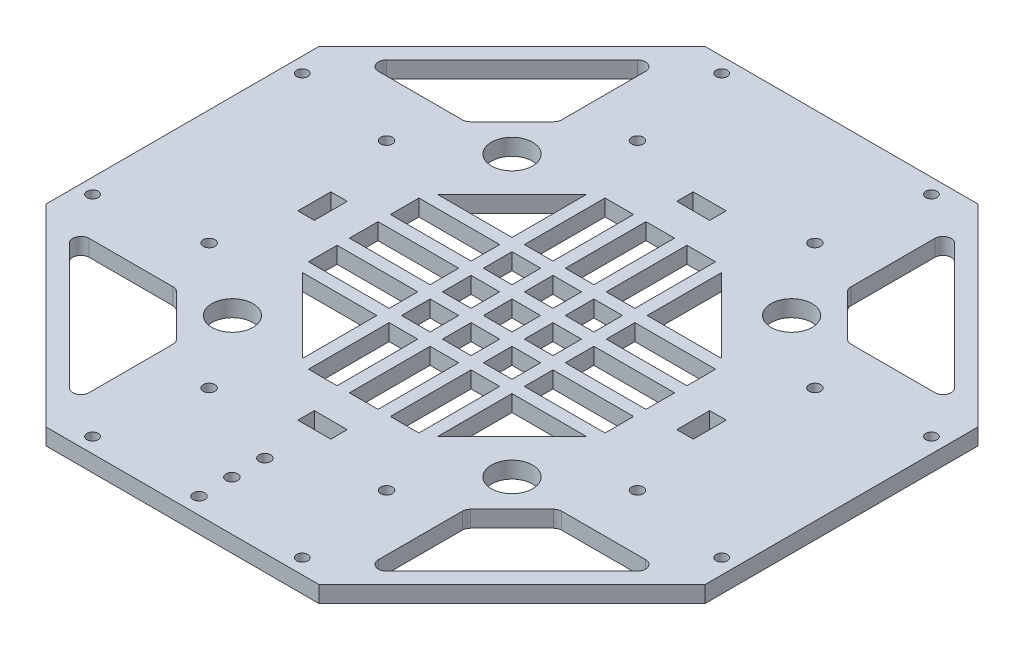
SolidWorks part; units mm, degrees
material "Custom Plastic"
ref_plane "Front Plane" through (0, 0, 0) normal (0, 0, 1) x (1, 0, 0)
ref_plane "Top Plane" through (0, 0, 0) normal (0, 1, 0) x (1, 0, 0)
ref_plane "Right Plane" through (0, 0, 0) normal (1, 0, 0) x (0, 0, -1)
ref_axis "Axis1" through (0, -0.2997, 0) along (0, 1, 0)
sketch "Base sketch" plane through (0, 0, 0) normal (0, 1, 0) x (1, 0, 0)
  line L1 (-127, 52.6051) -> (-127, -52.6051)
  line L2 (-127, -52.6051) -> (-52.6051, -127)
  line L3 (-52.6051, -127) -> (52.6051, -127)
  line L4 (52.6051, -127) -> (127, -52.6051)
  line L5 (127, -52.6051) -> (127, 52.6051)
  line L6 (127, 52.6051) -> (52.6051, 127)
  line L7 (52.6051, 127) -> (-52.6051, 127)
  line L8 (-52.6051, 127) -> (-127, 52.6051)
  circle A0 centre (0, 0) radius 127 construction
  dimension "D1" = 254
extrude "Base" add sketch "Base sketch" along normal blind 6.35
sketch "Sketch3" plane through (0, 6.35, 0) normal (0, 1, 0) x (1, 0, 0)
  line L0 (52.6051, 127) -> (-52.6051, 127) construction
  line L1 (-34.925, 114.3) -> (34.925, 114.3)
  line L2 (-34.925, 114.3) -> (-34.925, 79.375)
  line L4 (-34.925, 79.375) -> (34.925, 79.375)
  line L5 (34.925, 114.3) -> (34.925, 79.375)
  point P6 (0, 79.375)
  dimension "D1" = 69.85
  dimension "D2" = 34.925
  dimension "D3" = 12.7
sketch "Sketch4" plane through (0, 6.35, 0) normal (0, 1, 0) x (1, 0, 0)
  line L0 (0, 0) -> (0, 127) construction
  line L1 (52.6051, 127) -> (-52.6051, 127) construction
  line L4 (-6.35, 69.85) -> (6.35, 69.85)
  line L5 (-6.35, 69.85) -> (-6.35, 76.2)
  line L6 (-6.35, 76.2) -> (6.35, 76.2)
  line L7 (6.35, 69.85) -> (6.35, 76.2)
  line L8 (-6.35, 69.85) -> (6.35, 76.2) construction
  line L10 (-6.35, 76.2) -> (6.35, 69.85) construction
  point P5 (0, 73.025)
  dimension "D1" = 6.35
  dimension "D2" = 12.7
  dimension "D3" = 53.975
extrude "Support cutouts" cut sketch "Sketch4" against normal up to next
pattern_circular "Support cutout pattern" count 4 over 360 about axis through (0, -0.2997, 0) along (0, 1, 0) of "Support cutouts"
sketch "Sketch11" plane through (0, 6.35, 0) normal (0, 1, 0) x (1, 0, 0)
  line L1 (95.25, 39.4538) -> (39.4538, 95.25) construction
  line L2 (39.4538, 95.25) -> (-39.4538, 95.25) construction
  line L3 (-39.4538, 95.25) -> (-95.25, 39.4538) construction
  line L4 (-95.25, 39.4538) -> (-95.25, -39.4538) construction
  line L5 (-95.25, -39.4538) -> (-39.4538, -95.25) construction
  line L6 (-39.4538, -95.25) -> (39.4538, -95.25) construction
  line L7 (39.4538, -95.25) -> (95.25, -39.4538) construction
  line L8 (95.25, -39.4538) -> (95.25, 39.4538) construction
  line L9 (-34.1933, 82.55) -> (-82.55, 34.1933)
  line L10 (-82.55, 34.1933) -> (-82.55, -34.1933)
  line L11 (-82.55, -34.1933) -> (-34.1933, -82.55)
  line L12 (-34.1933, -82.55) -> (34.1933, -82.55)
  line L13 (34.1933, -82.55) -> (82.55, -34.1933)
  line L14 (82.55, -34.1933) -> (82.55, 34.1933)
  line L15 (82.55, 34.1933) -> (34.1933, 82.55)
  line L16 (34.1933, 82.55) -> (-34.1933, 82.55)
  circle A0 centre (0, 0) radius 95.25 construction
  circle A1 centre (0, 0) radius 82.55 construction
  dimension "D1" = 190.5
  dimension "D2" = 12.7
hole_wizard "#8 Clearance Hole1" positions "Sketch13" profile "Sketch12" hole size "#8" standard "ANSI Inch" end condition through all
sketch "Sketch13" plane through (0, 6.35, 0) normal (0, 1, 0) x (1, 0, 0)
  point P0 (-82.55, 34.1933)
  point P3 (-34.1933, 82.55)
  point P6 (34.1933, 82.55)
  point P9 (82.55, 34.1933)
  point P12 (82.55, -34.1933)
  point P15 (34.1933, -82.55)
  point P18 (-34.1933, -82.55)
  point P21 (-82.55, -34.1933)
sketch "Sketch12" plane through (-82.55, 6.35, -34.1933) normal (1, 0, 0) x (0, 0, 1)
  line L0 (0, 0) -> (0, 6.35)
  line L1 (0, 6.35) -> (2.2479, 6.35)
  line L2 (2.2479, 6.35) -> (2.2479, 0)
  line L5 (2.2479, 0) -> (0, 0)
  line L11 (0, -6.35) -> (0, 107.95) construction
  dimension "Thru Hole Dia." = 4.4958
  dimension "Thru Hole Depth" = 6.35
sketch "Sketch14" plane through (0, 6.35, 0) normal (0, 1, 0) x (1, 0, 0)
  circle A0 centre (-53.8815, 53.8815) radius 7.9375
  circle A1 centre (53.8815, 53.8815) radius 7.9375
  circle A2 centre (53.8815, -53.8815) radius 7.9375
  circle A3 centre (-53.8815, -53.8815) radius 7.9375
  point P13 (0, 0)
  dimension "D2" = 15.875
  dimension "D1" = 76.2
  dimension "D3" = 4
extrude "Cable holes" cut sketch "Sketch14" against normal up to next
sketch "Sketch15" plane through (0, 6.35, 0) normal (0, 1, 0) x (1, 0, 0)
  line L0 (0, -127) -> (0, 0) construction
  line L1 (-52.6051, -127) -> (52.6051, -127) construction
  point P5 (0, -120.65)
  point P6 (0, -107.95)
  point P7 (0, -95.25)
  dimension "D1" = 6.35
  dimension "D2" = 12.7
  dimension "D3" = 12.7
hole_wizard "#8 Clearance Hole2" positions "Sketch17" profile "Sketch16" hole size "#8" standard "ANSI Inch" end condition through all
sketch "Sketch17" plane through (0, 6.35, 0) normal (0, 1, 0) x (1, 0, 0)
  point P0 (0, -120.65)
  point P3 (0, -107.95)
  point P6 (0, -95.25)
sketch "Sketch16" plane through (0, 6.35, 120.65) normal (1, 0, 0) x (0, 0, 1)
  line L0 (0, 0) -> (0, 6.35)
  line L1 (0, 6.35) -> (2.2479, 6.35)
  line L2 (2.2479, 6.35) -> (2.2479, 0)
  line L5 (2.2479, 0) -> (0, 0)
  line L11 (0, -6.35) -> (0, 107.95) construction
  dimension "Thru Hole Dia." = 4.4958
  dimension "Thru Hole Depth" = 6.35
sketch "Sketch18" plane through (0, 6.35, 0) normal (0, 1, 0) x (1, 0, 0)
  line L0 (89.8026, 89.8026) -> (0, 0) construction
  line L1 (127, 52.6051) -> (52.6051, 127) construction
  line L2 (40.4112, 121.2335) -> (121.2335, 40.4112) construction
  point P7 (80.8223, 80.8223)
  dimension "D1" = 114.3
  dimension "D2" = 12.7
hole_wizard "plate mounting holes" positions "Sketch20" profile "Sketch19" hole size "#8" standard "ANSI Inch"
sketch "Sketch20" plane through (0, 6.35, 0) normal (0, 1, 0) x (1, 0, 0)
  point P0 (121.2335, 40.4112)
  point P7 (40.4112, 121.2335)
sketch "Sketch19" plane through (121.2335, 6.35, -40.4112) normal (1, 0, 0) x (0, 0, 1)
  line L0 (0, 0) -> (0, 6.351)
  line L1 (0, 6.351) -> (2.1526, 6.351)
  line L2 (2.1526, 6.351) -> (2.1526, 0)
  line L5 (2.1526, 0) -> (0, 0)
  line L10 (0, 6.351) -> (-2.1527, 6.351) construction
  line L11 (0, -6.35) -> (0, 107.95) construction
  dimension "Hole Dia." = 4.3053
  dimension "Hole Depth" = 6.351
  dimension "Drill Angle" = 180
pattern_circular "CirPattern1" count 4 over 360 about axis through (0, -0.2997, 0) along (0, 1, 0) of "plate mounting holes"
sketch "Sketch21" plane through (0, 6.35, 0) normal (0, 1, 0) x (1, 0, 0)
  line L0 (-6.35, 69.85) -> (6.35, 69.85) construction
  line L1 (-57.15, -23.6723) -> (-23.6723, -57.15)
  line L2 (-23.6723, -57.15) -> (23.6723, -57.15)
  line L3 (23.6723, -57.15) -> (57.15, -23.6723)
  line L4 (57.15, -23.6723) -> (57.15, 23.6723)
  line L5 (57.15, 23.6723) -> (23.6723, 57.15)
  line L6 (23.6723, 57.15) -> (-23.6723, 57.15)
  line L7 (-23.6723, 57.15) -> (-57.15, 23.6723)
  line L8 (-57.15, 23.6723) -> (-57.15, -23.6723)
  circle A0 centre (0, 0) radius 57.15 construction
  dimension "D1" = 114.3
extrude "Cut-Extrude1" cut sketch "Sketch21" against normal through all
sketch "Sketch24" plane through (0, 6.35, 0) normal (0, 1, 0) x (1, 0, 0)
  line L1 (-57.15, 23.6723) -> (57.15, 23.6723)
  line L2 (-57.15, -23.6723) -> (57.15, -23.6723)
  line L3 (57.15, 0) -> (-57.15, 0) construction
  line L4 (57.15, -23.6723) -> (57.15, 23.6723) construction
  line L5 (-57.15, 23.6723) -> (-57.15, -23.6723) construction
  line L6 (-57.15, 7.8908) -> (57.15, 7.8908)
  line L7 (-57.15, -7.8908) -> (57.15, -7.8908)
  dimension "D1" = 23.6723
  dimension "D2" = 15.7815
  dimension "D3" = 47.3446
sketch "Sketch26" plane through (0, 6.35, 0) normal (0, 1, 0) x (1, 0, 0)
  circle A0 centre (0, 19.05) radius 6.35
  dimension "D2" = 12.7
  dimension "D1" = 19.05
extrude "Extrude-Thin4" add sketch "Sketch24" against normal through all thin thin type mid plane wall 4.7625
pattern_circular "CirPattern4" count 2 every 90 about axis through (0, -0.2997, 0) along (0, 1, 0) of "Extrude-Thin4"
sketch "Sketch28" plane through (0, 6.35, 0) normal (0, 1, 0) x (1, 0, 0)
  line L0 (55.7414, -107.2183) -> (55.7414, -74.8894) construction
  line L1 (56.6713, -72.6443) -> (72.6443, -56.6713) construction
  line L2 (74.8894, -55.7414) -> (107.2183, -55.7414) construction
  line L3 (109.4634, -61.1615) -> (61.1615, -109.4634) construction
  line L4 (55.7414, -107.2183) -> (55.7414, -74.8894)
  line L5 (56.6713, -72.6443) -> (72.6443, -56.6713)
  line L6 (74.8894, -55.7414) -> (107.2183, -55.7414)
  line L7 (109.4634, -61.1615) -> (61.1615, -109.4634)
  line L8 (-72.6443, -56.6713) -> (-56.6713, -72.6443)
  line L9 (-107.2183, -55.7414) -> (-74.8894, -55.7414)
  line L10 (-61.1615, -109.4634) -> (-109.4634, -61.1615)
  line L11 (-55.7414, -74.8894) -> (-55.7414, -107.2183)
  line L12 (-56.6713, 72.6443) -> (-72.6443, 56.6713)
  line L13 (-55.7414, 107.2183) -> (-55.7414, 74.8894)
  line L14 (-109.4634, 61.1615) -> (-61.1615, 109.4634)
  line L15 (-74.8894, 55.7414) -> (-107.2183, 55.7414)
  line L16 (72.6443, 56.6713) -> (56.6713, 72.6443)
  line L17 (107.2183, 55.7414) -> (74.8894, 55.7414)
  line L18 (61.1615, 109.4634) -> (109.4634, 61.1615)
  line L19 (55.7414, 74.8894) -> (55.7414, 107.2183)
  arc A0 (56.6713, -72.6443) -> (55.7414, -74.8894) centre (58.9164, -74.8894) ccw construction
  arc A1 (74.8894, -55.7414) -> (72.6443, -56.6713) centre (74.8894, -58.9164) ccw construction
  arc A2 (109.4634, -61.1615) -> (107.2183, -55.7414) centre (107.2183, -58.9164) ccw construction
  arc A3 (55.7414, -107.2183) -> (61.1615, -109.4634) centre (58.9164, -107.2183) ccw construction
  arc A4 (56.6713, -72.6443) -> (55.7414, -74.8894) centre (58.9164, -74.8894) ccw
  arc A5 (74.8894, -55.7414) -> (72.6443, -56.6713) centre (74.8894, -58.9164) ccw
  arc A6 (109.4634, -61.1615) -> (107.2183, -55.7414) centre (107.2183, -58.9164) ccw
  arc A7 (55.7414, -107.2183) -> (61.1615, -109.4634) centre (58.9164, -107.2183) ccw
  arc A8 (-55.7414, -74.8894) -> (-56.6713, -72.6443) centre (-58.9164, -74.8894) ccw
  arc A9 (-72.6443, -56.6713) -> (-74.8894, -55.7414) centre (-74.8894, -58.9164) ccw
  arc A10 (-107.2183, -55.7414) -> (-109.4634, -61.1615) centre (-107.2183, -58.9164) ccw
  arc A11 (-61.1615, -109.4634) -> (-55.7414, -107.2183) centre (-58.9164, -107.2183) ccw
  arc A12 (-74.8894, 55.7414) -> (-72.6443, 56.6713) centre (-74.8894, 58.9164) ccw
  arc A13 (-56.6713, 72.6443) -> (-55.7414, 74.8894) centre (-58.9164, 74.8894) ccw
  arc A14 (-55.7414, 107.2183) -> (-61.1615, 109.4634) centre (-58.9164, 107.2183) ccw
  arc A15 (-109.4634, 61.1615) -> (-107.2183, 55.7414) centre (-107.2183, 58.9164) ccw
  arc A16 (55.7414, 74.8894) -> (56.6713, 72.6443) centre (58.9164, 74.8894) ccw
  arc A17 (72.6443, 56.6713) -> (74.8894, 55.7414) centre (74.8894, 58.9164) ccw
  arc A18 (107.2183, 55.7414) -> (109.4634, 61.1615) centre (107.2183, 58.9164) ccw
  arc A19 (61.1615, 109.4634) -> (55.7414, 107.2183) centre (58.9164, 107.2183) ccw
  point P51 (0, 0)
  dimension "D1" = 4
extrude "Cut-Extrude2" cut sketch "Sketch28" against normal through all
equation "\"MAT_THICKNESS\"=0.25"
equation "\"D1@Base\"=\"MAT_THICKNESS\""
equation "\"D1@Sketch4\"=\"MAT_THICKNESS\""
